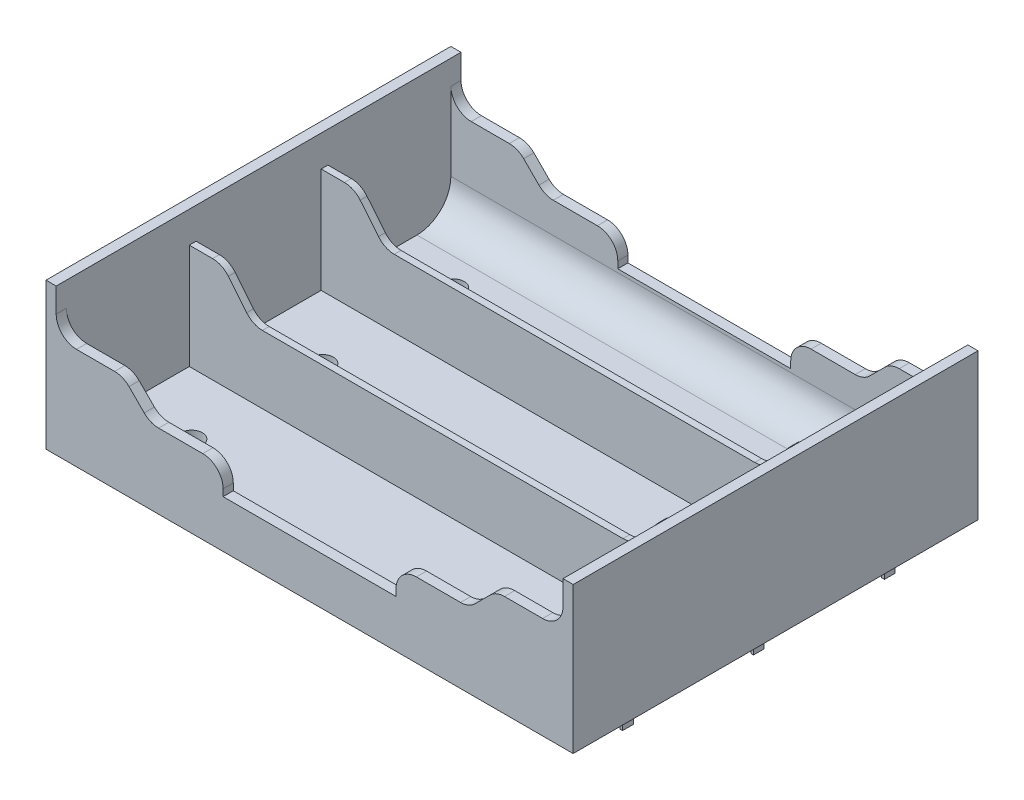
SolidWorks part; units mm, degrees
ref_plane "Front Plane" through (0, 0, 0) normal (0, 0, 1) x (1, 0, 0)
ref_plane "Top Plane" through (0, 0, 0) normal (0, 1, 0) x (1, 0, 0)
ref_plane "Right Plane" through (0, 0, 0) normal (1, 0, 0) x (0, 0, -1)
ref_plane "Plane1" through (0, 0, 0) normal (0, -1, 0) x (1, 0, 0)
sketch "Sketch1" plane through (0, 0, 0) normal (0, -1, 0) x (1, 0, 0)
  line L0 (-38.862, 29.845) -> (-38.862, -29.845)
  line L1 (-38.862, -29.845) -> (38.862, -29.845)
  line L2 (38.862, -29.845) -> (38.862, 29.845)
  line L3 (38.862, 29.845) -> (-38.862, 29.845)
extrude "Boss-Extrude1" add sketch "Sketch1" against normal blind 21.59
sketch "Sketch2" plane through (0, 0, 0) normal (0, -1, 0) x (1, 0, 0)
  line L0 (-35.9918, 0.7874) -> (-35.9918, -0.7874)
  line L1 (-35.9918, -0.7874) -> (-36.3982, -0.7874)
  line L2 (-36.3982, -0.7874) -> (-36.3982, 0.7874)
  line L3 (-36.3982, 0.7874) -> (-35.9918, 0.7874)
extrude "Boss-Extrude2" add sketch "Sketch2" along normal blind 3.175
sketch "Sketch3" plane through (0, 0, 0) normal (0, -1, 0) x (1, 0, 0)
  line L0 (36.3982, 0.7874) -> (36.3982, -0.7874)
  line L1 (36.3982, -0.7874) -> (35.9918, -0.7874)
  line L2 (35.9918, -0.7874) -> (35.9918, 0.7874)
  line L3 (35.9918, 0.7874) -> (36.3982, 0.7874)
extrude "Boss-Extrude3" add sketch "Sketch3" along normal blind 3.175
sketch "Sketch4" plane through (0, 0, 0) normal (0, -1, 0) x (1, 0, 0)
  line L0 (-35.9918, 20.0914) -> (-35.9918, 18.5166)
  line L1 (-35.9918, 18.5166) -> (-36.3982, 18.5166)
  line L2 (-36.3982, 18.5166) -> (-36.3982, 20.0914)
  line L3 (-36.3982, 20.0914) -> (-35.9918, 20.0914)
extrude "Boss-Extrude4" add sketch "Sketch4" along normal blind 3.175
sketch "Sketch5" plane through (0, 0, 0) normal (0, -1, 0) x (1, 0, 0)
  line L0 (36.3982, 20.0914) -> (36.3982, 18.5166)
  line L1 (36.3982, 18.5166) -> (35.9918, 18.5166)
  line L2 (35.9918, 18.5166) -> (35.9918, 20.0914)
  line L3 (35.9918, 20.0914) -> (36.3982, 20.0914)
extrude "Boss-Extrude5" add sketch "Sketch5" along normal blind 3.175
sketch "Sketch6" plane through (0, 0, 0) normal (0, -1, 0) x (1, 0, 0)
  line L0 (36.3982, -18.5166) -> (36.3982, -20.0914)
  line L1 (36.3982, -20.0914) -> (35.9918, -20.0914)
  line L2 (35.9918, -20.0914) -> (35.9918, -18.5166)
  line L3 (35.9918, -18.5166) -> (36.3982, -18.5166)
extrude "Boss-Extrude6" add sketch "Sketch6" along normal blind 3.175
sketch "Sketch7" plane through (0, 0, 0) normal (0, -1, 0) x (1, 0, 0)
  line L0 (-35.9918, -18.5166) -> (-35.9918, -20.0914)
  line L1 (-35.9918, -20.0914) -> (-36.3982, -20.0914)
  line L2 (-36.3982, -20.0914) -> (-36.3982, -18.5166)
  line L3 (-36.3982, -18.5166) -> (-35.9918, -18.5166)
extrude "Boss-Extrude7" add sketch "Sketch7" along normal blind 3.175
hole_wizard "#4 Clearance Hole1" positions "Sketch9" profile "Sketch8" hole size "#4" standard "ANSI Inch"
sketch "Sketch9" plane through (0, 0, 0) normal (0, -1, 0) x (-1, 0, 0)
  point P0 (27.94, 19.304)
  point P1 (27.94, 0)
  point P2 (-27.686, 19.304)
  point P3 (-27.686, 0)
  point P4 (-27.686, -19.304)
  point P5 (27.94, -19.304)
sketch "Sketch8" plane through (-27.94, 0, -19.304) normal (1, 0, 0) x (0, 0, -1)
  line L0 (0, 0) -> (0, 5.08)
  line L1 (0, 5.08) -> (1.6002, 5.08)
  line L2 (1.6002, 5.08) -> (1.6002, 0)
  line L5 (1.6002, 0) -> (0, 0)
  line L10 (0, 5.08) -> (-1.6002, 5.08) construction
  line L11 (0, -6.35) -> (0, 107.95) construction
  dimension "Hole Dia." = 3.2004
  dimension "Hole Depth" = 5.08
  dimension "Drill Angle" = 180
shell "Shell1" thickness 1.5 removed face at (0, 21.59, 0)
fillet "Fillet1" radius 5 2 edges at (0, 1.5, -28.345) (0, 1.5, 28.345)
sketch "Sketch10" plane through (0, 0, -29.845) normal (0, 0, -1) x (-1, 0, 0)
  line L0 (0, 7) -> (12.75, 7)
  line L1 (12.75, 7) -> (12.75, 11)
  line L2 (12.75, 11) -> (23.5, 11)
  line L3 (23.5, 11) -> (27.5, 15)
  line L4 (27.5, 15) -> (37.362, 15)
  line L5 (37.362, 21.59) -> (37.362, 6.5) construction
  line L6 (37.362, 15) -> (37.362, 21.59)
  line L7 (0, 0) -> (0, 21.59) construction
  line L8 (38.862, 21.59) -> (-38.862, 21.59) construction
  line L9 (38.862, 0) -> (-38.862, 0) construction
  line L10 (0, 7) -> (0, 21.59)
  line L11 (0, 21.59) -> (37.362, 21.59)
  dimension "D1" = 25.5
  dimension "D2" = 47
  dimension "D3" = 55
  dimension "D4" = 15
  dimension "D5" = 11
  dimension "D6" = 7
extrude "Cut-Extrude3" cut sketch "Sketch10" against normal through all contours L10 L11 L6 L4 L3 L2 L1 L0
mirror "Mirror1" about plane through (0, 0, 0) normal (1, 0, 0) of "Cut-Extrude3"
sketch "Sketch11" plane through (0, 1.5, 0) normal (0, 1, 0) x (1, 0, 0)
  line L1 (-37.362, 23.345) -> (37.362, 23.345)
  line L2 (-37.362, 23.345) -> (-37.362, -23.345)
  line L3 (-37.362, -23.345) -> (37.362, -23.345)
  line L4 (37.362, 23.345) -> (37.362, -23.345)
extrude "Cut-Extrude4" cut sketch "Sketch11" along normal through all
sketch "Sketch12" plane through (0, 1.5, 0) normal (0, 1, 0) x (1, 0, 0)
  line L0 (-37.362, -23.345) -> (-37.362, 23.345) construction
  line L1 (-37.362, 10.22) -> (37.362, 10.22)
  line L2 (-37.362, 10.22) -> (-37.362, 9.22)
  line L3 (-37.362, 9.22) -> (37.362, 9.22)
  line L4 (37.362, 10.22) -> (37.362, 9.22)
  line L5 (37.362, 23.345) -> (37.362, -23.345) construction
  line L6 (0, 0) -> (37.362, 0) construction
  line L7 (37.362, 29.845) -> (37.362, -29.845) construction
  dimension "D1" = 20.44
  dimension "D2" = 1
extrude "Boss-Extrude8" add sketch "Sketch12" along normal blind 15.5
sketch "Sketch13" plane through (0, 0, -9.22) normal (0, 0, 1) x (1, 0, 0)
  line L0 (-32.5, 17) -> (-28, 11.5)
  line L1 (-37.362, 17) -> (37.362, 17) construction
  line L2 (-28, 11.5) -> (28, 11.5)
  line L3 (28, 11.5) -> (32.5, 17)
  line L4 (-32.5, 17) -> (32.5, 17)
  point P4 (0, 11.5)
  point P7 (0, 17)
  dimension "D1" = 56
  dimension "D2" = 65
  dimension "D3" = 5.5
extrude "Cut-Extrude5" cut sketch "Sketch13" against normal up to next
mirror "Mirror2" about plane through (0, 0, 0) normal (0, 0, 1) of "Cut-Extrude5", "Boss-Extrude8"
fillet "Fillet2" radius 3 24 edges at (-37.362, 15, 29.095) (-28, 11.5, -9.72) (-32.5, 17, -9.72) (-32.5, 17, 9.72) (-28, 11.5, 9.72) (-37.362, 15, -29.095) (-27.5, 15, -29.095) (-23.5, 11, -29.095) (-12.75, 11, -29.095) (12.75, 11, -29.095) (23.5, 11, -29.095) (27.5, 15, -29.095) (37.362, 15, -29.095) (28, 11.5, -9.72) (32.5, 17, -9.72) (32.5, 17, 9.72) (28, 11.5, 9.72) (37.362, 15, 29.095) (23.5, 11, 29.095) (27.5, 15, 29.095) (12.75, 11, 29.095) (-12.75, 11, 29.095) (-23.5, 11, 29.095) (-27.5, 15, 29.095)
sketch "Sketch14" plane through (0, 1.5, 0) normal (0, 1, 0) x (1, 0, 0)
  circle A0 centre (21.1599, 16.5354) radius 1.9057
  text T0 "+"
extrude "Cut-Extrude6" cut sketch "Sketch14" against normal blind 0.2
pattern_linear "LPattern1" count 3 spacing 17.5 along (0, 0, 1) of "Cut-Extrude6"
ref_plane "Plane2" through (0, 0, -18.7825) normal (0, 0, 1) x (1, 0, 0)
ref_plane "Plane3" through (0, 0, 0.5) normal (0, 0, 1) x (1, 0, 0)
ref_plane "Plane4" through (0, 0, 20.0325) normal (0, 0, 1) x (1, 0, 0)
ref_plane "Plane5" through (0, 9.5, 0) normal (0, 1, 0) x (1, 0, 0)
ref_axis "Axis1" through (-41.0982, 9.5, -18.7825) along (1, 0, 0)
ref_axis "Axis2" through (-41.0982, 9.5, 0.5) along (1, 0, 0)
ref_axis "Axis3" through (-41.0982, 9.5, 20.0325) along (1, 0, 0)
